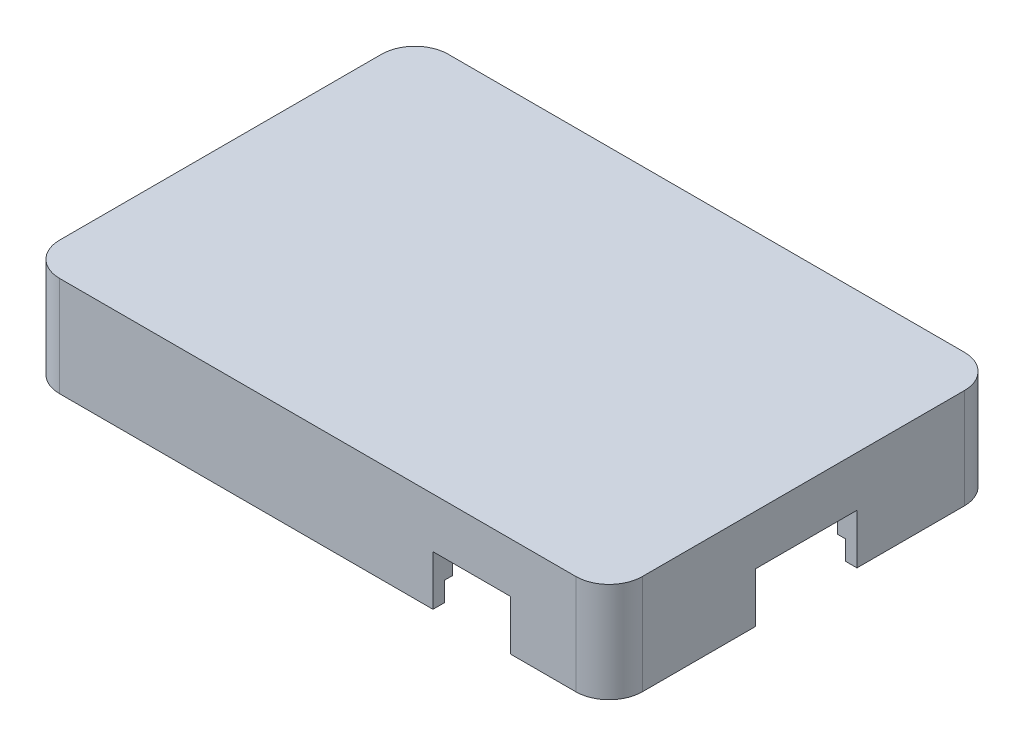
SolidWorks part; units mm, degrees
ref_plane "Front Plane" through (0, 0, 0) normal (0, 0, 1) x (1, 0, 0)
ref_plane "Top Plane" through (0, 0, 0) normal (0, 1, 0) x (1, 0, 0)
ref_plane "Right Plane" through (0, 0, 0) normal (1, 0, 0) x (0, 0, -1)
sketch "Sketch1" plane through (0, 0, 0) normal (0, 1, 0) x (1, 0, 0)
  line L1 (-52.5, 35) -> (52.5, 35)
  line L2 (-52.5, 35) -> (-52.5, -35)
  line L3 (-52.5, -35) -> (52.5, -35)
  line L4 (52.5, 35) -> (52.5, -35)
  line L5 (-52.5, 35) -> (52.5, -35) construction
  line L6 (-52.5, -35) -> (52.5, 35) construction
  point P0 (0, 0)
  dimension "D1" = 105
  dimension "D2" = 70
extrude "Boss-Extrude1" add sketch "Sketch1" along normal blind 15
sketch "Sketch3" plane through (0, 15, 0) normal (0, 1, 0) x (1, 0, 0)
  line L0 (52.5, -35) -> (52.5, 35) construction
  line L1 (49, -31.5) -> (-49, -31.5)
  line L2 (49, -31.5) -> (49, 31.5)
  line L3 (49, 31.5) -> (-49, 31.5)
  line L4 (-49, -31.5) -> (-49, 31.5)
  line L5 (49, -31.5) -> (-49, 31.5) construction
  line L6 (49, 31.5) -> (-49, -31.5) construction
  line L7 (-52.5, -35) -> (52.5, -35) construction
  point P0 (0, 0)
  dimension "D1" = 3.5
  dimension "D2" = 3.5
extrude "Cut-Extrude1" cut sketch "Sketch3" against normal blind 12
fillet "Fillet1" radius 6 8 edges at (-52.5, 7.5, -35) (-52.5, 7.5, 35) (52.5, 7.5, -35) (52.5, 7.5, 35) (49, 9, -31.5) (-49, 9, -31.5) (-49, 9, 31.5) (49, 9, 31.5)
sketch "Sketch4" plane through (0, 3, 0) normal (0, 1, 0) x (1, 0, 0)
  line L0 (-43, -31.5) -> (43, -31.5) construction
  line L1 (49, -25.5) -> (49, 25.5) construction
  circle A0 centre (40, -22.5) radius 3.5
  circle A1 centre (40, 19.2) radius 3.5
  circle A2 centre (-36.1, -22.5) radius 3.5
  circle A3 centre (-36.1, 19.2) radius 3.5
  dimension "D5" = 7
  dimension "D6" = 76.1
  dimension "D1" = 41.7
  dimension "D2" = 9
  dimension "D3" = 76.1
  dimension "D4" = 9
  dimension "D7" = 41.7
extrude "Boss-Extrude2" [suppressed] add sketch "Sketch4" along normal blind 5
sketch "Sketch5" [suppressed] plane through (0, 8, 0) normal (0, 1, 0) x (1, 0, 0)
  circle A0 centre (-36.1, 19.2) radius 1
  circle A1 centre (-36.1, -22.5) radius 1
  circle A2 centre (40, -22.5) radius 1
  circle A3 centre (40, 19.0603) radius 1
  dimension "D1" = 2
extrude "Cut-Extrude2" [suppressed] cut sketch "Sketch5" against normal blind 8
sketch "Sketch6" plane through (0, 15, 0) normal (0, 1, 0) x (1, 0, 0)
  line L0 (49, -25.5) -> (49, 25.5) construction
  line L1 (49, 9.66) -> (52.5, 9.66)
  line L2 (49, 9.66) -> (49, -8.64)
  line L3 (49, -8.64) -> (52.5, -8.64)
  line L4 (52.5, 9.66) -> (52.5, -8.64)
  line L5 (52.5, -29) -> (52.5, 29) construction
  line L6 (-46.5, -35) -> (46.5, -35) construction
  line L7 (34.76, -35) -> (20.76, -35)
  line L8 (34.76, -35) -> (34.76, -31.5)
  line L9 (34.76, -31.5) -> (20.76, -31.5)
  line L10 (20.76, -35) -> (20.76, -31.5)
  line L11 (-43, -31.5) -> (43, -31.5) construction
  line L12 (-52.5, 29) -> (-52.5, -29) construction
  line L13 (-52.5, 10) -> (-49, 10)
  line L14 (-52.5, 10) -> (-52.5, -10)
  line L15 (-52.5, -10) -> (-49, -10)
  line L16 (-49, 10) -> (-49, -10)
  line L17 (-49, 25.5) -> (-49, -25.5) construction
  dimension "D1" = 14
  dimension "D2" = 20
  dimension "D3" = 25
  dimension "D4" = 14.24
  dimension "D5" = 22.86
  dimension "D6" = 18.3
extrude "Cut-Extrude3" cut sketch "Sketch6" against normal blind 26
sketch "Sketch9" plane through (0, 3, 0) normal (0, 1, 0) x (1, 0, 0)
  line L1 (-43, 31.5) -> (43, 31.5)
  line L2 (-49, 25.5) -> (-49, -25.5)
  line L3 (-43, -31.5) -> (43, -31.5)
  line L4 (49, 25.5) -> (49, -25.5)
  line L5 (-49, 31.5) -> (49, -31.5) construction
  line L6 (-49, -31.5) -> (49, 31.5) construction
  line L7 (-43, -31.5) -> (20.76, -31.5) construction
  arc A0 (-43, 31.5) -> (-49, 25.5) centre (-43, 25.5) ccw
  arc A1 (43, 31.5) -> (49, 25.5) centre (43, 25.5) cw
  arc A2 (43, -31.5) -> (49, -25.5) centre (43, -25.5) ccw
  arc A3 (-49, -25.5) -> (-43, -31.5) centre (-43, -25.5) ccw
  point P0 (0, 0)
  dimension "D3" = 6
  dimension "D2" = 0
extrude "Cut-Extrude4" cut sketch "Sketch9" against normal blind 10
sketch "Sketch10" plane through (0, 15, 0) normal (0, 1, 0) x (1, 0, 0)
  line L0 (-52.5, -10) -> (-52.5, -29) construction
  line L1 (-46.5, 35) -> (46.5, 35)
  line L2 (-52.5, 29) -> (-52.5, -29)
  line L3 (-46.5, -35) -> (46.5, -35)
  line L4 (52.5, 29) -> (52.5, -29)
  line L5 (-52.5, 35) -> (52.5, -35) construction
  line L6 (-52.5, -35) -> (52.5, 35) construction
  line L7 (-46.5, -35) -> (20.76, -35) construction
  arc A0 (46.5, -35) -> (52.5, -29) centre (46.5, -29) ccw
  arc A1 (46.5, 35) -> (52.5, 29) centre (46.5, 29) cw
  arc A2 (-46.5, 35) -> (-52.5, 29) centre (-46.5, 29) ccw
  arc A3 (-52.5, -29) -> (-46.5, -35) centre (-46.5, -29) ccw
  point P0 (0, 0)
  dimension "D3" = 6
  dimension "D1" = 0
  dimension "D2" = 0
extrude "Boss-Extrude3" add sketch "Sketch10" along normal blind 3
sketch "Sketch11" plane through (0, 0, 0) normal (0, -1, 0) x (-1, 0, 0)
  line L0 (-46.5, 35) -> (46.5, 35) construction
  line L1 (-44.4, 32.9) -> (44.4, 32.9)
  line L2 (-50.4, 26.9) -> (-50.4, -26.9)
  line L3 (-44.4, -32.9) -> (44.4, -32.9)
  line L4 (50.4, 26.9) -> (50.4, -26.9)
  line L5 (-50.4, 32.9) -> (50.4, -32.9) construction
  line L6 (-50.4, -32.9) -> (50.4, 32.9) construction
  line L7 (-52.5, -29) -> (-52.5, -8.64) construction
  arc A0 (44.4, -32.9) -> (50.4, -26.9) centre (44.4, -26.9) ccw
  arc A1 (44.4, 32.9) -> (50.4, 26.9) centre (44.4, 26.9) cw
  arc A2 (-44.4, 32.9) -> (-50.4, 26.9) centre (-44.4, 26.9) ccw
  arc A3 (-50.4, -26.9) -> (-44.4, -32.9) centre (-44.4, -26.9) ccw
  point P0 (0, 0)
  dimension "D3" = 6
  dimension "D1" = 2.1
  dimension "D2" = 2.1
extrude "Cut-Extrude5" cut sketch "Sketch11" against normal blind 3.5
sketch "Sketch12" plane through (0, 15, 0) normal (0, -1, 0) x (-1, 0, 0)
  line L1 (-52.5, 9.66) -> (-49, 9.66)
  line L2 (-52.5, 9.66) -> (-52.5, -8.64)
  line L3 (-52.5, -8.64) -> (-49, -8.64)
  line L4 (-49, 9.66) -> (-49, -8.64)
  line L5 (-20.76, -35) -> (-34.76, -35)
  line L6 (-20.76, -35) -> (-20.76, -31.5)
  line L7 (-20.76, -31.5) -> (-34.76, -31.5)
  line L8 (-34.76, -35) -> (-34.76, -31.5)
  line L9 (49, -10) -> (52.5, -10)
  line L10 (49, -10) -> (49, 10)
  line L11 (49, 10) -> (52.5, 10)
  line L12 (52.5, -10) -> (52.5, 10)
extrude "Boss-Extrude4" add sketch "Sketch12" along normal blind 6
equation "\"D2@Sketch3\"=\"D1@Sketch3\""
equation "\"D4@Sketch4\"=\"D2@Sketch4\""
equation "\"D6@Sketch4\"=\"D3@Sketch4\""
equation "\"D7@Sketch4\"=\"D1@Sketch4\""
